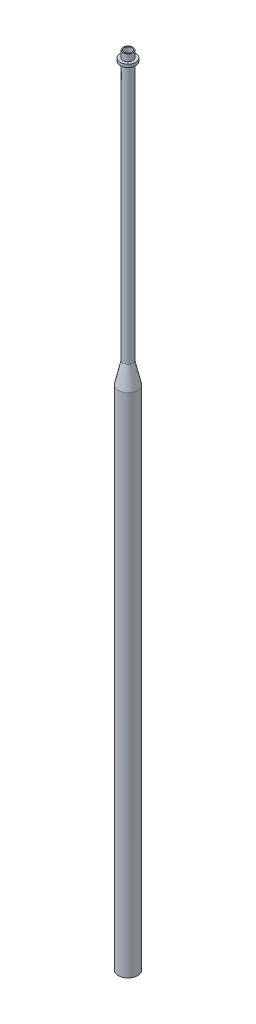
SolidWorks part; units mm, degrees
ref_plane "Plan de face" through (0, 0, 0) normal (0, 0, 1) x (1, 0, 0)
ref_plane "Plan de dessus" through (0, 0, 0) normal (0, 1, 0) x (1, 0, 0)
ref_plane "Plan de droite" through (0, 0, 0) normal (1, 0, 0) x (0, 0, -1)
sketch "Esquisse1" plane through (0, 0, 0) normal (0, 1, 0) x (1, 0, 0)
  circle A0 centre (0, 0) radius 5
  dimension "D1" = 10
extrude "Boss.-Extru.1" add sketch "Esquisse1" along normal blind 820
sketch "Esquisse2" plane through (0, 0, 0) normal (0, 1, 0) x (1, 0, 0)
  circle A0 centre (0, 0) radius 10
  dimension "D1" = 20
extrude "Boss.-Extru.2" add sketch "Esquisse2" along normal blind 500
chamfer "Chanfrein1" distance 10 angle 77 1 edges at (0, 500, 5) first distance on face at (0, 500, 5)
sketch "Esquisse3" plane through (0, 820, 0) normal (0, 1, 0) x (1, 0, 0)
  circle A0 centre (0, 0) radius 4
  dimension "D1" = 8
extrude "Enlèv. mat.-Extru.1" cut sketch "Esquisse3" against normal through all
sketch3d "Esquisse3D1" plane through (0, 0, 0) normal (0, 0, 1) x (1, 0, 0)
  dimension "D1" = 10
sketch "Esquisse4" plane through (0, 810, 0) normal (0, 1, 0) x (1, 0, 0)
  circle A0 centre (0, 0) radius 8
  circle A1 centre (0, 0) radius 4.5
  circle A2 centre (0, 0) radius 5 construction
  dimension "D1" = 9
  dimension "D2" = 3
extrude "Boss.-Extru.3" add sketch "Esquisse4" along normal blind 3
